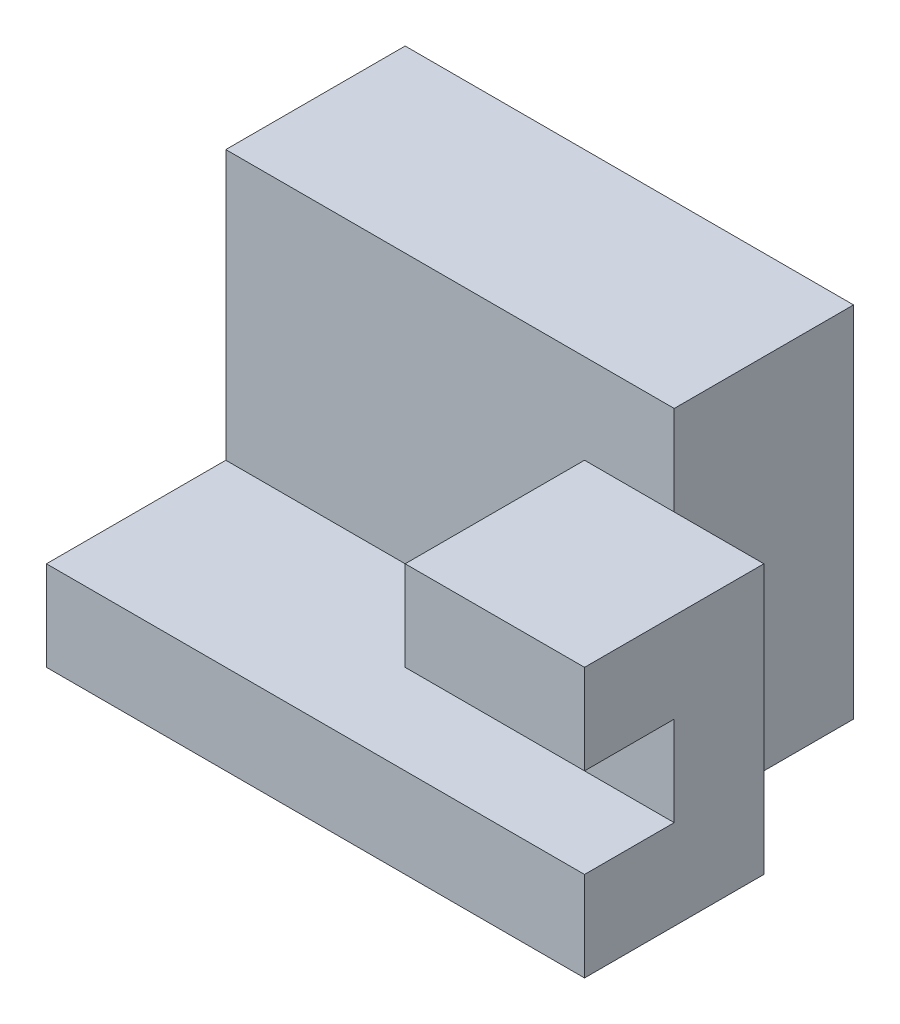
SolidWorks part; units mm, degrees
ref_plane "Front Plane" through (0, 0, 0) normal (0, 0, 1) x (1, 0, 0)
ref_plane "Top Plane" through (0, 0, 0) normal (0, 1, 0) x (1, 0, 0)
ref_plane "Right Plane" through (0, 0, 0) normal (1, 0, 0) x (0, 0, -1)
sketch "Sketch1" plane through (0, 0, 0) normal (0, 1, 0) x (1, 0, 0)
  line L0 (0, 0) -> (0, 1016)
  line L1 (0, 1016) -> (1270, 1016)
  line L2 (1270, 1016) -> (1270, 508)
  line L3 (1270, 508) -> (1524, 508)
  line L4 (1524, 508) -> (1524, 0)
  line L5 (1524, 0) -> (1016, 0)
  line L6 (1016, 0) -> (1016, 508)
  line L7 (1016, 508) -> (1270, 508)
  line L8 (1016, 508) -> (0, 508)
  line L9 (1016, 0) -> (0, 0)
  dimension "D1" = 1016
  dimension "D2" = 1270
  dimension "D3" = 508
  dimension "D4" = 1524
extrude "Boss-Extrude1" add sketch "Sketch1" along normal blind 254 contours L9 L6 L8 L0 region at (508, 0, -254)
extrude "Boss-Extrude2" add sketch "Sketch1<3>" along normal blind 1016 contours L8 L7 L2 L1 L0 region at (635, 0, -762)
sketch "Sketch1<3>" plane through (0, 0, 0) normal (0, 1, 0) x (1, 0, 0) same geometry as "Sketch1"
extrude "Boss-Extrude3" add sketch "Sketch1<4>" along normal blind 762 contours L7 L6 L5 L4 L3 region at (1270, 0, -254)
sketch "Sketch1<4>" plane through (0, 0, 0) normal (0, 1, 0) x (1, 0, 0) same geometry as "Sketch1"
sketch "Sketch2" plane through (1016, 0, 0) normal (-1, 0, 0) x (0, 0, 1)
  line L0 (-254, 254) -> (-254, 508)
  line L1 (0, 254) -> (-508, 254) construction
  line L2 (-254, 508) -> (0, 508)
  line L3 (0, 762) -> (0, 254) construction
  line L4 (-254, 254) -> (0, 254)
  line L5 (0, 254) -> (0, 508)
extrude "Cut-Extrude3" cut sketch "Sketch2" against normal blind 508
